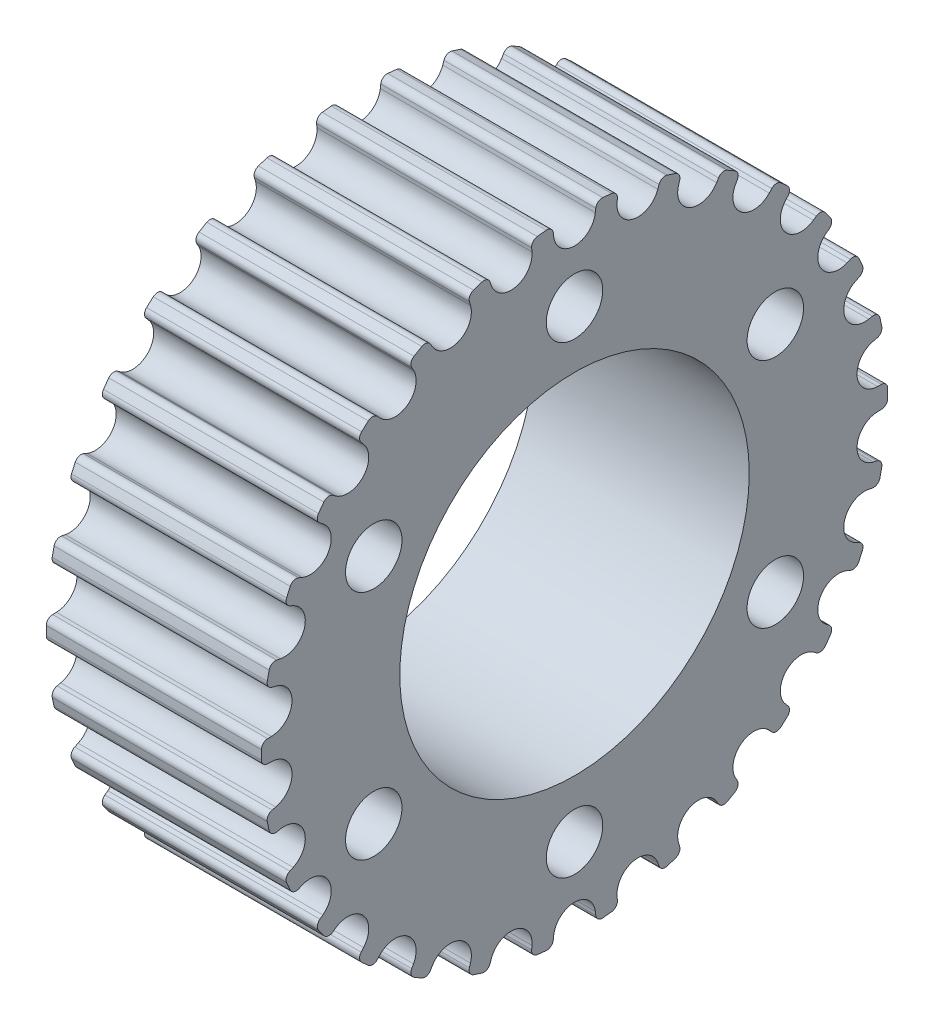
SolidWorks part; units mm, degrees
ref_plane "前视基准面" through (0, 0, 0) normal (0, 0, 1) x (1, 0, 0)
ref_plane "上视基准面" through (0, 0, 0) normal (0, 1, 0) x (1, 0, 0)
ref_plane "右视基准面" through (0, 0, 0) normal (1, 0, 0) x (0, 0, -1)
sketch "草图1" plane through (0, 0, 0) normal (0, 0, 1) x (1, 0, 0)
  line L0 (0, 0) -> (64.8368, 0) construction
  line L1 (0, 2.7506) -> (0, 23.303)
  line L2 (0, 23.303) -> (16, 23.303)
  line L3 (16, 23.303) -> (16, 5.5012)
  line L4 (16, 5.5012) -> (20, 5.5012)
  line L5 (20, 5.5012) -> (20, 2.7506)
  line L6 (20, 2.7506) -> (0, 2.7506)
  dimension "L" = 20
  dimension "B" = 16
  dimension "d" = 5.5012
  dimension "d1" = 11.0024
  dimension "da" = 46.606
revolve "旋转1" add sketch "草图1" angle 360 about L0
ref_axis "基准轴1" through (-1, 0, 0) along (1, 0, 0)
sketch "草图6" plane through (0, 0, 0) normal (1, 0, 0) x (0, 0, -1)
  line L0 (0, 0) -> (0, 30.6512) construction
  line L1 (1.5822, 22.7885) -> (1.5484, 22.5129)
  line L2 (2.5795, 23.1598) -> (2.7761, 24.7614)
  line L3 (-2.5795, 23.1598) -> (-2.7761, 24.7614)
  line L4 (-1.5822, 22.7885) -> (-1.5484, 22.5129)
  circle A0 centre (0, 0) radius 23.303 construction
  circle A1 centre (0, 0) radius 21.143 construction
  arc A2 (-1.5484, 22.5129) -> (1.5484, 22.5129) centre (0, 22.703) ccw
  arc A3 (2.7761, 24.7614) -> (-2.7761, 24.7614) centre (0, 0) ccw
  arc A4 (1.5822, 22.7885) -> (2.1019, 23.208) centre (2.0586, 22.73) cw
  arc A5 (2.1019, 23.208) -> (2.5795, 23.1598) centre (0, 0) cw
  arc A6 (-2.1019, 23.208) -> (-2.5795, 23.1598) centre (0, 0) ccw
  arc A7 (-1.5822, 22.7885) -> (-2.1019, 23.208) centre (-2.0586, 22.73) ccw
  point P7 (0, 3.25)
  point P8 (0, 28.4912)
  point P15 (1.6383, 23.2453)
  dimension "D1" = 42.286
  dimension "ra" = 0.48
  dimension "rf" = 1.56
  dimension "hg" = 2.16
  dimension "D3" = 0.48
  dimension "D4" = 1.6136
  dimension "angle" = 14
  dimension "bw" = 3.25
extrude "切除-拉伸2" cut sketch "草图6" along normal up to next
pattern_circular "阵列(圆周)3" count 30 over 360 about axis through (-1, 0, 0) along (1, 0, 0) of "切除-拉伸2"
sketch "草图7" plane through (16, 0, 0) normal (1, 0, 0) x (0, 0, -1)
  line L60 (1.5822, 22.7885) -> (1.5484, 22.5129)
  line L61 (-1.5484, 22.5129) -> (-1.5822, 22.7885)
  line L62 (-3.1904, 22.6194) -> (-3.1662, 22.3428)
  line L63 (-6.1952, 21.699) -> (-6.2856, 21.9615)
  line L64 (-7.8235, 21.4618) -> (-7.7423, 21.1963)
  line L65 (-10.5713, 19.9368) -> (-10.7143, 20.1748)
  line L66 (-12.1147, 19.3663) -> (-11.9801, 19.1234)
  line L67 (-14.4854, 17.3032) -> (-14.6748, 17.5063)
  line L68 (-15.8764, 16.4243) -> (-15.6943, 16.2147)
  line L69 (-17.7664, 13.9134) -> (-17.9938, 14.0726)
  line L70 (-18.9443, 12.7645) -> (-18.7225, 12.5974)
  line L71 (-20.2709, 9.9155) -> (-20.5265, 10.024)
  line L72 (-21.1842, 8.5468) -> (-20.9326, 8.4295)
  line L73 (-21.8895, 5.4843) -> (-22.162, 5.5373)
  line L74 (-22.4982, 3.9556) -> (-22.2277, 3.8931)
  line L75 (-22.5514, 0.8133) -> (-22.829, 0.8085)
  line L76 (-22.829, -0.8085) -> (-22.5514, -0.8133)
  line L77 (-22.2277, -3.8931) -> (-22.4982, -3.9556)
  line L78 (-22.162, -5.5373) -> (-21.8895, -5.4843)
  line L79 (-20.9326, -8.4295) -> (-21.1842, -8.5468)
  line L80 (-20.5265, -10.024) -> (-20.2709, -9.9155)
  line L81 (-18.7225, -12.5974) -> (-18.9443, -12.7645)
  line L82 (-17.9938, -14.0726) -> (-17.7664, -13.9134)
  line L83 (-15.6943, -16.2147) -> (-15.8764, -16.4243)
  line L84 (-14.6748, -17.5063) -> (-14.4854, -17.3032)
  line L85 (-11.9801, -19.1234) -> (-12.1147, -19.3663)
  line L86 (-10.7143, -20.1748) -> (-10.5713, -19.9368)
  line L87 (-7.7423, -21.1963) -> (-7.8235, -21.4618)
  line L88 (-6.2856, -21.9615) -> (-6.1952, -21.699)
  line L89 (-3.1662, -22.3428) -> (-3.1904, -22.6194)
  line L90 (-1.5822, -22.7885) -> (-1.5484, -22.5129)
  line L91 (1.5484, -22.5129) -> (1.5822, -22.7885)
  line L92 (3.1904, -22.6194) -> (3.1662, -22.3428)
  line L93 (6.1952, -21.699) -> (6.2856, -21.9615)
  line L94 (7.8235, -21.4618) -> (7.7423, -21.1963)
  line L95 (10.5713, -19.9368) -> (10.7143, -20.1748)
  line L96 (12.1147, -19.3663) -> (11.9801, -19.1234)
  line L97 (14.4854, -17.3032) -> (14.6748, -17.5063)
  line L98 (15.8764, -16.4243) -> (15.6943, -16.2147)
  line L99 (17.7664, -13.9134) -> (17.9938, -14.0726)
  line L100 (18.9443, -12.7645) -> (18.7225, -12.5974)
  line L101 (20.2709, -9.9155) -> (20.5265, -10.024)
  line L102 (21.1842, -8.5468) -> (20.9326, -8.4295)
  line L103 (21.8895, -5.4843) -> (22.162, -5.5373)
  line L104 (22.4982, -3.9556) -> (22.2277, -3.8931)
  line L105 (22.5514, -0.8133) -> (22.829, -0.8085)
  line L106 (22.829, 0.8085) -> (22.5514, 0.8133)
  line L107 (22.2277, 3.8931) -> (22.4982, 3.9556)
  line L108 (22.162, 5.5373) -> (21.8895, 5.4843)
  line L109 (20.9326, 8.4295) -> (21.1842, 8.5468)
  line L110 (20.5265, 10.024) -> (20.2709, 9.9155)
  line L111 (18.7225, 12.5974) -> (18.9443, 12.7645)
  line L112 (17.9938, 14.0726) -> (17.7664, 13.9134)
  line L113 (15.6943, 16.2147) -> (15.8764, 16.4243)
  line L114 (14.6748, 17.5063) -> (14.4854, 17.3032)
  line L115 (11.9801, 19.1234) -> (12.1147, 19.3663)
  line L116 (10.7143, 20.1748) -> (10.5713, 19.9368)
  line L117 (7.7423, 21.1963) -> (7.8235, 21.4618)
  line L118 (6.2856, 21.9615) -> (6.1952, 21.699)
  line L119 (3.1662, 22.3428) -> (3.1904, 22.6194)
  line L120 (1.5822, 22.7885) -> (1.5484, 22.5129)
  line L121 (-1.5484, 22.5129) -> (-1.5822, 22.7885)
  line L122 (-3.1904, 22.6194) -> (-3.1662, 22.3428)
  line L123 (-6.1952, 21.699) -> (-6.2856, 21.9615)
  line L124 (-7.8235, 21.4618) -> (-7.7423, 21.1963)
  line L125 (-10.5713, 19.9368) -> (-10.7143, 20.1748)
  line L126 (-12.1147, 19.3663) -> (-11.9801, 19.1234)
  line L127 (-14.4854, 17.3032) -> (-14.6748, 17.5063)
  line L128 (-15.8764, 16.4243) -> (-15.6943, 16.2147)
  line L129 (-17.7664, 13.9134) -> (-17.9938, 14.0726)
  line L130 (-18.9443, 12.7645) -> (-18.7225, 12.5974)
  line L131 (-20.2709, 9.9155) -> (-20.5265, 10.024)
  line L132 (-21.1842, 8.5468) -> (-20.9326, 8.4295)
  line L133 (-21.8895, 5.4843) -> (-22.162, 5.5373)
  line L134 (-22.4982, 3.9556) -> (-22.2277, 3.8931)
  line L135 (-22.5514, 0.8133) -> (-22.829, 0.8085)
  line L136 (-22.829, -0.8085) -> (-22.5514, -0.8133)
  line L137 (-22.2277, -3.8931) -> (-22.4982, -3.9556)
  line L138 (-22.162, -5.5373) -> (-21.8895, -5.4843)
  line L139 (-20.9326, -8.4295) -> (-21.1842, -8.5468)
  line L140 (-20.5265, -10.024) -> (-20.2709, -9.9155)
  line L141 (-18.7225, -12.5974) -> (-18.9443, -12.7645)
  line L142 (-17.9938, -14.0726) -> (-17.7664, -13.9134)
  line L143 (-15.6943, -16.2147) -> (-15.8764, -16.4243)
  line L144 (-14.6748, -17.5063) -> (-14.4854, -17.3032)
  line L145 (-11.9801, -19.1234) -> (-12.1147, -19.3663)
  line L146 (-10.7143, -20.1748) -> (-10.5713, -19.9368)
  line L147 (-7.7423, -21.1963) -> (-7.8235, -21.4618)
  line L148 (-6.2856, -21.9615) -> (-6.1952, -21.699)
  line L149 (-3.1662, -22.3428) -> (-3.1904, -22.6194)
  line L150 (-1.5822, -22.7885) -> (-1.5484, -22.5129)
  line L151 (1.5484, -22.5129) -> (1.5822, -22.7885)
  line L152 (3.1904, -22.6194) -> (3.1662, -22.3428)
  line L153 (6.1952, -21.699) -> (6.2856, -21.9615)
  line L154 (7.8235, -21.4618) -> (7.7423, -21.1963)
  line L155 (10.5713, -19.9368) -> (10.7143, -20.1748)
  line L156 (12.1147, -19.3663) -> (11.9801, -19.1234)
  line L157 (14.4854, -17.3032) -> (14.6748, -17.5063)
  line L158 (15.8764, -16.4243) -> (15.6943, -16.2147)
  line L159 (17.7664, -13.9134) -> (17.9938, -14.0726)
  line L160 (18.9443, -12.7645) -> (18.7225, -12.5974)
  line L161 (20.2709, -9.9155) -> (20.5265, -10.024)
  line L162 (21.1842, -8.5468) -> (20.9326, -8.4295)
  line L163 (21.8895, -5.4843) -> (22.162, -5.5373)
  line L164 (22.4982, -3.9556) -> (22.2277, -3.8931)
  line L165 (22.5514, -0.8133) -> (22.829, -0.8085)
  line L166 (22.829, 0.8085) -> (22.5514, 0.8133)
  line L167 (22.2277, 3.8931) -> (22.4982, 3.9556)
  line L168 (22.162, 5.5373) -> (21.8895, 5.4843)
  line L169 (20.9326, 8.4295) -> (21.1842, 8.5468)
  line L170 (20.5265, 10.024) -> (20.2709, 9.9155)
  line L171 (18.7225, 12.5974) -> (18.9443, 12.7645)
  line L172 (17.9938, 14.0726) -> (17.7664, 13.9134)
  line L173 (15.6943, 16.2147) -> (15.8764, 16.4243)
  line L174 (14.6748, 17.5063) -> (14.4854, 17.3032)
  line L175 (11.9801, 19.1234) -> (12.1147, 19.3663)
  line L176 (10.7143, 20.1748) -> (10.5713, 19.9368)
  line L177 (7.7423, 21.1963) -> (7.8235, 21.4618)
  line L178 (6.2856, 21.9615) -> (6.1952, 21.699)
  line L179 (3.1662, 22.3428) -> (3.1904, 22.6194)
  circle A0 centre (0, 0) radius 13
  circle A1 centre (0, 0) radius 17.25 construction
  circle A2 centre (0, 17.25) radius 2.1
  circle A3 centre (14.9389, 8.625) radius 2.1
  circle A4 centre (14.9389, -8.625) radius 2.1
  circle A5 centre (0, -17.25) radius 2.1
  circle A6 centre (-14.9389, -8.625) radius 2.1
  circle A7 centre (-14.9389, 8.625) radius 2.1
  arc A120 (3.1904, 22.6194) -> (2.7692, 23.1379) centre (2.7122, 22.6613) ccw
  arc A121 (2.7692, 23.1379) -> (2.1019, 23.208) centre (0, 0) ccw
  arc A122 (2.1019, 23.208) -> (1.5822, 22.7885) centre (2.0586, 22.73) ccw
  arc A123 (-1.5484, 22.5129) -> (1.5484, 22.5129) centre (0, 22.703) ccw
  arc A124 (-1.5822, 22.7885) -> (-2.1019, 23.208) centre (-2.0586, 22.73) ccw
  arc A125 (-2.1019, 23.208) -> (-2.7692, 23.1379) centre (0, 0) ccw
  arc A126 (-2.7692, 23.1379) -> (-3.1904, 22.6194) centre (-2.7122, 22.6613) ccw
  arc A127 (-6.1952, 21.699) -> (-3.1662, 22.3428) centre (-4.7202, 22.2069) ccw
  arc A128 (-6.2856, 21.9615) -> (-6.8812, 22.2638) centre (-6.7395, 21.8052) ccw
  arc A129 (-6.8812, 22.2638) -> (-7.5193, 22.0565) centre (0, 0) ccw
  arc A130 (-7.5193, 22.0565) -> (-7.8235, 21.4618) centre (-7.3645, 21.6022) ccw
  arc A131 (-10.5713, 19.9368) -> (-7.7423, 21.1963) centre (-9.2341, 20.7402) ccw
  arc A132 (-10.7143, 20.1748) -> (-11.3598, 20.3466) centre (-11.1258, 19.9275) ccw
  arc A133 (-11.3598, 20.3466) -> (-11.9408, 20.0112) centre (0, 0) ccw
  arc A134 (-11.9408, 20.0112) -> (-12.1147, 19.3663) centre (-11.6949, 19.599) ccw
  arc A135 (-14.4854, 17.3032) -> (-11.9801, 19.1234) centre (-13.3445, 18.3671) ccw
  arc A136 (-14.6748, 17.5063) -> (-15.3418, 17.5402) centre (-15.0258, 17.1789) ccw
  arc A137 (-15.3418, 17.5402) -> (-15.8404, 17.0912) centre (0, 0) ccw
  arc A138 (-15.8404, 17.0912) -> (-15.8764, 16.4243) centre (-15.5142, 16.7392) ccw
  arc A139 (-17.7664, 13.9134) -> (-15.6943, 16.2147) centre (-16.8716, 15.1913) ccw
  arc A140 (-17.9938, 14.0726) -> (-18.6534, 13.9672) centre (-18.2691, 13.6795) ccw
  arc A141 (-18.6534, 13.9672) -> (-19.0478, 13.4243) centre (0, 0) ccw
  arc A142 (-19.0478, 13.4243) -> (-18.9443, 12.7645) centre (-18.6554, 13.1478) ccw
  arc A143 (-20.2709, 9.9155) -> (-18.7225, 12.5974) centre (-19.6614, 11.3515) ccw
  arc A144 (-20.5265, 10.024) -> (-21.1497, 9.7837) centre (-20.714, 9.5822) ccw
  arc A145 (-21.1497, 9.7837) -> (-21.4226, 9.1707) centre (0, 0) ccw
  arc A146 (-21.4226, 9.1707) -> (-21.1842, 8.5468) centre (-20.9813, 8.9818) ccw
  arc A147 (-21.8895, 5.4843) -> (-20.9326, 8.4295) centre (-21.5918, 7.0156) ccw
  arc A148 (-22.162, 5.5373) -> (-22.7217, 5.1726) centre (-22.2536, 5.0661) ccw
  arc A149 (-22.7217, 5.1726) -> (-22.8612, 4.5163) centre (0, 0) ccw
  arc A150 (-22.8612, 4.5163) -> (-22.4982, 3.9556) centre (-22.3903, 4.4233) ccw
  arc A151 (-22.5514, 0.8133) -> (-22.2277, 3.8931) centre (-22.5786, 2.3731) ccw
  arc A152 (-22.829, 0.8085) -> (-23.3006, 0.3355) centre (-22.8206, 0.3286) ccw
  arc A153 (-23.3006, 0.3355) -> (-23.3006, -0.3355) centre (0, 0) ccw
  arc A154 (-23.3006, -0.3355) -> (-22.829, -0.8085) centre (-22.8206, -0.3286) ccw
  arc A155 (-22.2277, -3.8931) -> (-22.5514, -0.8133) centre (-22.5786, -2.3731) ccw
  arc A156 (-22.4982, -3.9556) -> (-22.8612, -4.5163) centre (-22.3903, -4.4233) ccw
  arc A157 (-22.8612, -4.5163) -> (-22.7217, -5.1726) centre (0, 0) ccw
  arc A158 (-22.7217, -5.1726) -> (-22.162, -5.5373) centre (-22.2536, -5.0661) ccw
  arc A159 (-20.9326, -8.4295) -> (-21.8895, -5.4843) centre (-21.5918, -7.0156) ccw
  arc A160 (-21.1842, -8.5468) -> (-21.4226, -9.1707) centre (-20.9813, -8.9818) ccw
  arc A161 (-21.4226, -9.1707) -> (-21.1497, -9.7837) centre (0, 0) ccw
  arc A162 (-21.1497, -9.7837) -> (-20.5265, -10.024) centre (-20.714, -9.5822) ccw
  arc A163 (-18.7225, -12.5974) -> (-20.2709, -9.9155) centre (-19.6614, -11.3515) ccw
  arc A164 (-18.9443, -12.7645) -> (-19.0478, -13.4243) centre (-18.6554, -13.1478) ccw
  arc A165 (-19.0478, -13.4243) -> (-18.6534, -13.9672) centre (0, 0) ccw
  arc A166 (-18.6534, -13.9672) -> (-17.9938, -14.0726) centre (-18.2691, -13.6795) ccw
  arc A167 (-15.6943, -16.2147) -> (-17.7664, -13.9134) centre (-16.8716, -15.1913) ccw
  arc A168 (-15.8764, -16.4243) -> (-15.8404, -17.0912) centre (-15.5142, -16.7392) ccw
  arc A169 (-15.8404, -17.0912) -> (-15.3418, -17.5402) centre (0, 0) ccw
  arc A170 (-15.3418, -17.5402) -> (-14.6748, -17.5063) centre (-15.0258, -17.1789) ccw
  arc A171 (-11.9801, -19.1234) -> (-14.4854, -17.3032) centre (-13.3445, -18.3671) ccw
  arc A172 (-12.1147, -19.3663) -> (-11.9408, -20.0112) centre (-11.6949, -19.599) ccw
  arc A173 (-11.9408, -20.0112) -> (-11.3598, -20.3466) centre (0, 0) ccw
  arc A174 (-11.3598, -20.3466) -> (-10.7143, -20.1748) centre (-11.1258, -19.9275) ccw
  arc A175 (-7.7423, -21.1963) -> (-10.5713, -19.9368) centre (-9.2341, -20.7402) ccw
  arc A176 (-7.8235, -21.4618) -> (-7.5193, -22.0565) centre (-7.3645, -21.6022) ccw
  arc A177 (-7.5193, -22.0565) -> (-6.8812, -22.2638) centre (0, 0) ccw
  arc A178 (-6.8812, -22.2638) -> (-6.2856, -21.9615) centre (-6.7395, -21.8052) ccw
  arc A179 (-3.1662, -22.3428) -> (-6.1952, -21.699) centre (-4.7202, -22.2069) ccw
  arc A180 (-3.1904, -22.6194) -> (-2.7692, -23.1379) centre (-2.7122, -22.6613) ccw
  arc A181 (-2.7692, -23.1379) -> (-2.1019, -23.208) centre (0, 0) ccw
  arc A182 (-2.1019, -23.208) -> (-1.5822, -22.7885) centre (-2.0586, -22.73) ccw
  arc A183 (1.5484, -22.5129) -> (-1.5484, -22.5129) centre (0, -22.703) ccw
  arc A184 (1.5822, -22.7885) -> (2.1019, -23.208) centre (2.0586, -22.73) ccw
  arc A185 (2.1019, -23.208) -> (2.7692, -23.1379) centre (0, 0) ccw
  arc A186 (2.7692, -23.1379) -> (3.1904, -22.6194) centre (2.7122, -22.6613) ccw
  arc A187 (6.1952, -21.699) -> (3.1662, -22.3428) centre (4.7202, -22.2069) ccw
  arc A188 (6.2856, -21.9615) -> (6.8812, -22.2638) centre (6.7395, -21.8052) ccw
  arc A189 (6.8812, -22.2638) -> (7.5193, -22.0565) centre (0, 0) ccw
  arc A190 (7.5193, -22.0565) -> (7.8235, -21.4618) centre (7.3645, -21.6022) ccw
  arc A191 (10.5713, -19.9368) -> (7.7423, -21.1963) centre (9.2341, -20.7402) ccw
  arc A192 (10.7143, -20.1748) -> (11.3598, -20.3466) centre (11.1258, -19.9275) ccw
  arc A193 (11.3598, -20.3466) -> (11.9408, -20.0112) centre (0, 0) ccw
  arc A194 (11.9408, -20.0112) -> (12.1147, -19.3663) centre (11.6949, -19.599) ccw
  arc A195 (14.4854, -17.3032) -> (11.9801, -19.1234) centre (13.3445, -18.3671) ccw
  arc A196 (14.6748, -17.5063) -> (15.3418, -17.5402) centre (15.0258, -17.1789) ccw
  arc A197 (15.3418, -17.5402) -> (15.8404, -17.0912) centre (0, 0) ccw
  arc A198 (15.8404, -17.0912) -> (15.8764, -16.4243) centre (15.5142, -16.7392) ccw
  arc A199 (17.7664, -13.9134) -> (15.6943, -16.2147) centre (16.8716, -15.1913) ccw
  arc A200 (17.9938, -14.0726) -> (18.6534, -13.9672) centre (18.2691, -13.6795) ccw
  arc A201 (18.6534, -13.9672) -> (19.0478, -13.4243) centre (0, 0) ccw
  arc A202 (19.0478, -13.4243) -> (18.9443, -12.7645) centre (18.6554, -13.1478) ccw
  arc A203 (20.2709, -9.9155) -> (18.7225, -12.5974) centre (19.6614, -11.3515) ccw
  arc A204 (20.5265, -10.024) -> (21.1497, -9.7837) centre (20.714, -9.5822) ccw
  arc A205 (21.1497, -9.7837) -> (21.4226, -9.1707) centre (0, 0) ccw
  arc A206 (21.4226, -9.1707) -> (21.1842, -8.5468) centre (20.9813, -8.9818) ccw
  arc A207 (21.8895, -5.4843) -> (20.9326, -8.4295) centre (21.5918, -7.0156) ccw
  arc A208 (22.162, -5.5373) -> (22.7217, -5.1726) centre (22.2536, -5.0661) ccw
  arc A209 (22.7217, -5.1726) -> (22.8612, -4.5163) centre (0, 0) ccw
  arc A210 (22.8612, -4.5163) -> (22.4982, -3.9556) centre (22.3903, -4.4233) ccw
  arc A211 (22.5514, -0.8133) -> (22.2277, -3.8931) centre (22.5786, -2.3731) ccw
  arc A212 (22.829, -0.8085) -> (23.3006, -0.3355) centre (22.8206, -0.3286) ccw
  arc A213 (23.3006, -0.3355) -> (23.3006, 0.3355) centre (0, 0) ccw
  arc A214 (23.3006, 0.3355) -> (22.829, 0.8085) centre (22.8206, 0.3286) ccw
  arc A215 (22.2277, 3.8931) -> (22.5514, 0.8133) centre (22.5786, 2.3731) ccw
  arc A216 (22.4982, 3.9556) -> (22.8612, 4.5163) centre (22.3903, 4.4233) ccw
  arc A217 (22.8612, 4.5163) -> (22.7217, 5.1726) centre (0, 0) ccw
  arc A218 (22.7217, 5.1726) -> (22.162, 5.5373) centre (22.2536, 5.0661) ccw
  arc A219 (20.9326, 8.4295) -> (21.8895, 5.4843) centre (21.5918, 7.0156) ccw
  arc A220 (21.1842, 8.5468) -> (21.4226, 9.1707) centre (20.9813, 8.9818) ccw
  arc A221 (21.4226, 9.1707) -> (21.1497, 9.7837) centre (0, 0) ccw
  arc A222 (21.1497, 9.7837) -> (20.5265, 10.024) centre (20.714, 9.5822) ccw
  arc A223 (18.7225, 12.5974) -> (20.2709, 9.9155) centre (19.6614, 11.3515) ccw
  arc A224 (18.9443, 12.7645) -> (19.0478, 13.4243) centre (18.6554, 13.1478) ccw
  arc A225 (19.0478, 13.4243) -> (18.6534, 13.9672) centre (0, 0) ccw
  arc A226 (18.6534, 13.9672) -> (17.9938, 14.0726) centre (18.2691, 13.6795) ccw
  arc A227 (15.6943, 16.2147) -> (17.7664, 13.9134) centre (16.8716, 15.1913) ccw
  arc A228 (15.8764, 16.4243) -> (15.8404, 17.0912) centre (15.5142, 16.7392) ccw
  arc A229 (15.8404, 17.0912) -> (15.3418, 17.5402) centre (0, 0) ccw
  arc A230 (15.3418, 17.5402) -> (14.6748, 17.5063) centre (15.0258, 17.1789) ccw
  arc A231 (11.9801, 19.1234) -> (14.4854, 17.3032) centre (13.3445, 18.3671) ccw
  arc A232 (12.1147, 19.3663) -> (11.9408, 20.0112) centre (11.6949, 19.599) ccw
  arc A233 (11.9408, 20.0112) -> (11.3598, 20.3466) centre (0, 0) ccw
  arc A234 (11.3598, 20.3466) -> (10.7143, 20.1748) centre (11.1258, 19.9275) ccw
  arc A235 (7.7423, 21.1963) -> (10.5713, 19.9368) centre (9.2341, 20.7402) ccw
  arc A236 (7.8235, 21.4618) -> (7.5193, 22.0565) centre (7.3645, 21.6022) ccw
  arc A237 (7.5193, 22.0565) -> (6.8812, 22.2638) centre (0, 0) ccw
  arc A238 (6.8812, 22.2638) -> (6.2856, 21.9615) centre (6.7395, 21.8052) ccw
  arc A239 (3.1662, 22.3428) -> (6.1952, 21.699) centre (4.7202, 22.2069) ccw
  arc A240 (3.1904, 22.6194) -> (2.7692, 23.1379) centre (2.7122, 22.6613) ccw
  arc A241 (2.7692, 23.1379) -> (2.1019, 23.208) centre (0, 0) ccw
  arc A242 (2.1019, 23.208) -> (1.5822, 22.7885) centre (2.0586, 22.73) ccw
  arc A243 (-1.5484, 22.5129) -> (1.5484, 22.5129) centre (0, 22.703) ccw
  arc A244 (-1.5822, 22.7885) -> (-2.1019, 23.208) centre (-2.0586, 22.73) ccw
  arc A245 (-2.1019, 23.208) -> (-2.7692, 23.1379) centre (0, 0) ccw
  arc A246 (-2.7692, 23.1379) -> (-3.1904, 22.6194) centre (-2.7122, 22.6613) ccw
  arc A247 (-6.1952, 21.699) -> (-3.1662, 22.3428) centre (-4.7202, 22.2069) ccw
  arc A248 (-6.2856, 21.9615) -> (-6.8812, 22.2638) centre (-6.7395, 21.8052) ccw
  arc A249 (-6.8812, 22.2638) -> (-7.5193, 22.0565) centre (0, 0) ccw
  arc A250 (-7.5193, 22.0565) -> (-7.8235, 21.4618) centre (-7.3645, 21.6022) ccw
  arc A251 (-10.5713, 19.9368) -> (-7.7423, 21.1963) centre (-9.2341, 20.7402) ccw
  arc A252 (-10.7143, 20.1748) -> (-11.3598, 20.3466) centre (-11.1258, 19.9275) ccw
  arc A253 (-11.3598, 20.3466) -> (-11.9408, 20.0112) centre (0, 0) ccw
  arc A254 (-11.9408, 20.0112) -> (-12.1147, 19.3663) centre (-11.6949, 19.599) ccw
  arc A255 (-14.4854, 17.3032) -> (-11.9801, 19.1234) centre (-13.3445, 18.3671) ccw
  arc A256 (-14.6748, 17.5063) -> (-15.3418, 17.5402) centre (-15.0258, 17.1789) ccw
  arc A257 (-15.3418, 17.5402) -> (-15.8404, 17.0912) centre (0, 0) ccw
  arc A258 (-15.8404, 17.0912) -> (-15.8764, 16.4243) centre (-15.5142, 16.7392) ccw
  arc A259 (-17.7664, 13.9134) -> (-15.6943, 16.2147) centre (-16.8716, 15.1913) ccw
  arc A260 (-17.9938, 14.0726) -> (-18.6534, 13.9672) centre (-18.2691, 13.6795) ccw
  arc A261 (-18.6534, 13.9672) -> (-19.0478, 13.4243) centre (0, 0) ccw
  arc A262 (-19.0478, 13.4243) -> (-18.9443, 12.7645) centre (-18.6554, 13.1478) ccw
  arc A263 (-20.2709, 9.9155) -> (-18.7225, 12.5974) centre (-19.6614, 11.3515) ccw
  arc A264 (-20.5265, 10.024) -> (-21.1497, 9.7837) centre (-20.714, 9.5822) ccw
  arc A265 (-21.1497, 9.7837) -> (-21.4226, 9.1707) centre (0, 0) ccw
  arc A266 (-21.4226, 9.1707) -> (-21.1842, 8.5468) centre (-20.9813, 8.9818) ccw
  arc A267 (-21.8895, 5.4843) -> (-20.9326, 8.4295) centre (-21.5918, 7.0156) ccw
  arc A268 (-22.162, 5.5373) -> (-22.7217, 5.1726) centre (-22.2536, 5.0661) ccw
  arc A269 (-22.7217, 5.1726) -> (-22.8612, 4.5163) centre (0, 0) ccw
  arc A270 (-22.8612, 4.5163) -> (-22.4982, 3.9556) centre (-22.3903, 4.4233) ccw
  arc A271 (-22.5514, 0.8133) -> (-22.2277, 3.8931) centre (-22.5786, 2.3731) ccw
  arc A272 (-22.829, 0.8085) -> (-23.3006, 0.3355) centre (-22.8206, 0.3286) ccw
  arc A273 (-23.3006, 0.3355) -> (-23.3006, -0.3355) centre (0, 0) ccw
  arc A274 (-23.3006, -0.3355) -> (-22.829, -0.8085) centre (-22.8206, -0.3286) ccw
  arc A275 (-22.2277, -3.8931) -> (-22.5514, -0.8133) centre (-22.5786, -2.3731) ccw
  arc A276 (-22.4982, -3.9556) -> (-22.8612, -4.5163) centre (-22.3903, -4.4233) ccw
  arc A277 (-22.8612, -4.5163) -> (-22.7217, -5.1726) centre (0, 0) ccw
  arc A278 (-22.7217, -5.1726) -> (-22.162, -5.5373) centre (-22.2536, -5.0661) ccw
  arc A279 (-20.9326, -8.4295) -> (-21.8895, -5.4843) centre (-21.5918, -7.0156) ccw
  arc A280 (-21.1842, -8.5468) -> (-21.4226, -9.1707) centre (-20.9813, -8.9818) ccw
  arc A281 (-21.4226, -9.1707) -> (-21.1497, -9.7837) centre (0, 0) ccw
  arc A282 (-21.1497, -9.7837) -> (-20.5265, -10.024) centre (-20.714, -9.5822) ccw
  arc A283 (-18.7225, -12.5974) -> (-20.2709, -9.9155) centre (-19.6614, -11.3515) ccw
  arc A284 (-18.9443, -12.7645) -> (-19.0478, -13.4243) centre (-18.6554, -13.1478) ccw
  arc A285 (-19.0478, -13.4243) -> (-18.6534, -13.9672) centre (0, 0) ccw
  arc A286 (-18.6534, -13.9672) -> (-17.9938, -14.0726) centre (-18.2691, -13.6795) ccw
  arc A287 (-15.6943, -16.2147) -> (-17.7664, -13.9134) centre (-16.8716, -15.1913) ccw
  arc A288 (-15.8764, -16.4243) -> (-15.8404, -17.0912) centre (-15.5142, -16.7392) ccw
  arc A289 (-15.8404, -17.0912) -> (-15.3418, -17.5402) centre (0, 0) ccw
  arc A290 (-15.3418, -17.5402) -> (-14.6748, -17.5063) centre (-15.0258, -17.1789) ccw
  arc A291 (-11.9801, -19.1234) -> (-14.4854, -17.3032) centre (-13.3445, -18.3671) ccw
  arc A292 (-12.1147, -19.3663) -> (-11.9408, -20.0112) centre (-11.6949, -19.599) ccw
  arc A293 (-11.9408, -20.0112) -> (-11.3598, -20.3466) centre (0, 0) ccw
  arc A294 (-11.3598, -20.3466) -> (-10.7143, -20.1748) centre (-11.1258, -19.9275) ccw
  arc A295 (-7.7423, -21.1963) -> (-10.5713, -19.9368) centre (-9.2341, -20.7402) ccw
  arc A296 (-7.8235, -21.4618) -> (-7.5193, -22.0565) centre (-7.3645, -21.6022) ccw
  arc A297 (-7.5193, -22.0565) -> (-6.8812, -22.2638) centre (0, 0) ccw
  arc A298 (-6.8812, -22.2638) -> (-6.2856, -21.9615) centre (-6.7395, -21.8052) ccw
  arc A299 (-3.1662, -22.3428) -> (-6.1952, -21.699) centre (-4.7202, -22.2069) ccw
  arc A300 (-3.1904, -22.6194) -> (-2.7692, -23.1379) centre (-2.7122, -22.6613) ccw
  arc A301 (-2.7692, -23.1379) -> (-2.1019, -23.208) centre (0, 0) ccw
  arc A302 (-2.1019, -23.208) -> (-1.5822, -22.7885) centre (-2.0586, -22.73) ccw
  arc A303 (1.5484, -22.5129) -> (-1.5484, -22.5129) centre (0, -22.703) ccw
  arc A304 (1.5822, -22.7885) -> (2.1019, -23.208) centre (2.0586, -22.73) ccw
  arc A305 (2.1019, -23.208) -> (2.7692, -23.1379) centre (0, 0) ccw
  arc A306 (2.7692, -23.1379) -> (3.1904, -22.6194) centre (2.7122, -22.6613) ccw
  arc A307 (6.1952, -21.699) -> (3.1662, -22.3428) centre (4.7202, -22.2069) ccw
  arc A308 (6.2856, -21.9615) -> (6.8812, -22.2638) centre (6.7395, -21.8052) ccw
  arc A309 (6.8812, -22.2638) -> (7.5193, -22.0565) centre (0, 0) ccw
  arc A310 (7.5193, -22.0565) -> (7.8235, -21.4618) centre (7.3645, -21.6022) ccw
  arc A311 (10.5713, -19.9368) -> (7.7423, -21.1963) centre (9.2341, -20.7402) ccw
  arc A312 (10.7143, -20.1748) -> (11.3598, -20.3466) centre (11.1258, -19.9275) ccw
  arc A313 (11.3598, -20.3466) -> (11.9408, -20.0112) centre (0, 0) ccw
  arc A314 (11.9408, -20.0112) -> (12.1147, -19.3663) centre (11.6949, -19.599) ccw
  arc A315 (14.4854, -17.3032) -> (11.9801, -19.1234) centre (13.3445, -18.3671) ccw
  arc A316 (14.6748, -17.5063) -> (15.3418, -17.5402) centre (15.0258, -17.1789) ccw
  arc A317 (15.3418, -17.5402) -> (15.8404, -17.0912) centre (0, 0) ccw
  arc A318 (15.8404, -17.0912) -> (15.8764, -16.4243) centre (15.5142, -16.7392) ccw
  arc A319 (17.7664, -13.9134) -> (15.6943, -16.2147) centre (16.8716, -15.1913) ccw
  arc A320 (17.9938, -14.0726) -> (18.6534, -13.9672) centre (18.2691, -13.6795) ccw
  arc A321 (18.6534, -13.9672) -> (19.0478, -13.4243) centre (0, 0) ccw
  arc A322 (19.0478, -13.4243) -> (18.9443, -12.7645) centre (18.6554, -13.1478) ccw
  arc A323 (20.2709, -9.9155) -> (18.7225, -12.5974) centre (19.6614, -11.3515) ccw
  arc A324 (20.5265, -10.024) -> (21.1497, -9.7837) centre (20.714, -9.5822) ccw
  arc A325 (21.1497, -9.7837) -> (21.4226, -9.1707) centre (0, 0) ccw
  arc A326 (21.4226, -9.1707) -> (21.1842, -8.5468) centre (20.9813, -8.9818) ccw
  arc A327 (21.8895, -5.4843) -> (20.9326, -8.4295) centre (21.5918, -7.0156) ccw
  arc A328 (22.162, -5.5373) -> (22.7217, -5.1726) centre (22.2536, -5.0661) ccw
  arc A329 (22.7217, -5.1726) -> (22.8612, -4.5163) centre (0, 0) ccw
  arc A330 (22.8612, -4.5163) -> (22.4982, -3.9556) centre (22.3903, -4.4233) ccw
  arc A331 (22.5514, -0.8133) -> (22.2277, -3.8931) centre (22.5786, -2.3731) ccw
  arc A332 (22.829, -0.8085) -> (23.3006, -0.3355) centre (22.8206, -0.3286) ccw
  arc A333 (23.3006, -0.3355) -> (23.3006, 0.3355) centre (0, 0) ccw
  arc A334 (23.3006, 0.3355) -> (22.829, 0.8085) centre (22.8206, 0.3286) ccw
  arc A335 (22.2277, 3.8931) -> (22.5514, 0.8133) centre (22.5786, 2.3731) ccw
  arc A336 (22.4982, 3.9556) -> (22.8612, 4.5163) centre (22.3903, 4.4233) ccw
  arc A337 (22.8612, 4.5163) -> (22.7217, 5.1726) centre (0, 0) ccw
  arc A338 (22.7217, 5.1726) -> (22.162, 5.5373) centre (22.2536, 5.0661) ccw
  arc A339 (20.9326, 8.4295) -> (21.8895, 5.4843) centre (21.5918, 7.0156) ccw
  arc A340 (21.1842, 8.5468) -> (21.4226, 9.1707) centre (20.9813, 8.9818) ccw
  arc A341 (21.4226, 9.1707) -> (21.1497, 9.7837) centre (0, 0) ccw
  arc A342 (21.1497, 9.7837) -> (20.5265, 10.024) centre (20.714, 9.5822) ccw
  arc A343 (18.7225, 12.5974) -> (20.2709, 9.9155) centre (19.6614, 11.3515) ccw
  arc A344 (18.9443, 12.7645) -> (19.0478, 13.4243) centre (18.6554, 13.1478) ccw
  arc A345 (19.0478, 13.4243) -> (18.6534, 13.9672) centre (0, 0) ccw
  arc A346 (18.6534, 13.9672) -> (17.9938, 14.0726) centre (18.2691, 13.6795) ccw
  arc A347 (15.6943, 16.2147) -> (17.7664, 13.9134) centre (16.8716, 15.1913) ccw
  arc A348 (15.8764, 16.4243) -> (15.8404, 17.0912) centre (15.5142, 16.7392) ccw
  arc A349 (15.8404, 17.0912) -> (15.3418, 17.5402) centre (0, 0) ccw
  arc A350 (15.3418, 17.5402) -> (14.6748, 17.5063) centre (15.0258, 17.1789) ccw
  arc A351 (11.9801, 19.1234) -> (14.4854, 17.3032) centre (13.3445, 18.3671) ccw
  arc A352 (12.1147, 19.3663) -> (11.9408, 20.0112) centre (11.6949, 19.599) ccw
  arc A353 (11.9408, 20.0112) -> (11.3598, 20.3466) centre (0, 0) ccw
  arc A354 (11.3598, 20.3466) -> (10.7143, 20.1748) centre (11.1258, 19.9275) ccw
  arc A355 (7.7423, 21.1963) -> (10.5713, 19.9368) centre (9.2341, 20.7402) ccw
  arc A356 (7.8235, 21.4618) -> (7.5193, 22.0565) centre (7.3645, 21.6022) ccw
  arc A357 (7.5193, 22.0565) -> (6.8812, 22.2638) centre (0, 0) ccw
  arc A358 (6.8812, 22.2638) -> (6.2856, 21.9615) centre (6.7395, 21.8052) ccw
  arc A359 (3.1662, 22.3428) -> (6.1952, 21.699) centre (4.7202, 22.2069) ccw
  point P67 (0, 0)
  dimension "D2" = 34.5
  dimension "D3" = 26
  dimension "D4" = 4.2
  dimension "D1" = 0
  dimension "D5" = 6
extrude "切除-拉伸3" cut sketch "草图7" against normal mid plane 118 contours A0 | A3 | A4 | A5 | A6 | A7 | A2
equation "\"D1@草图6\" = \"da@草图1\"  - \"hg@草图6\" - \"hg@草图6\""
equation "\"D3@草图6\" = \"ra@草图6\""
